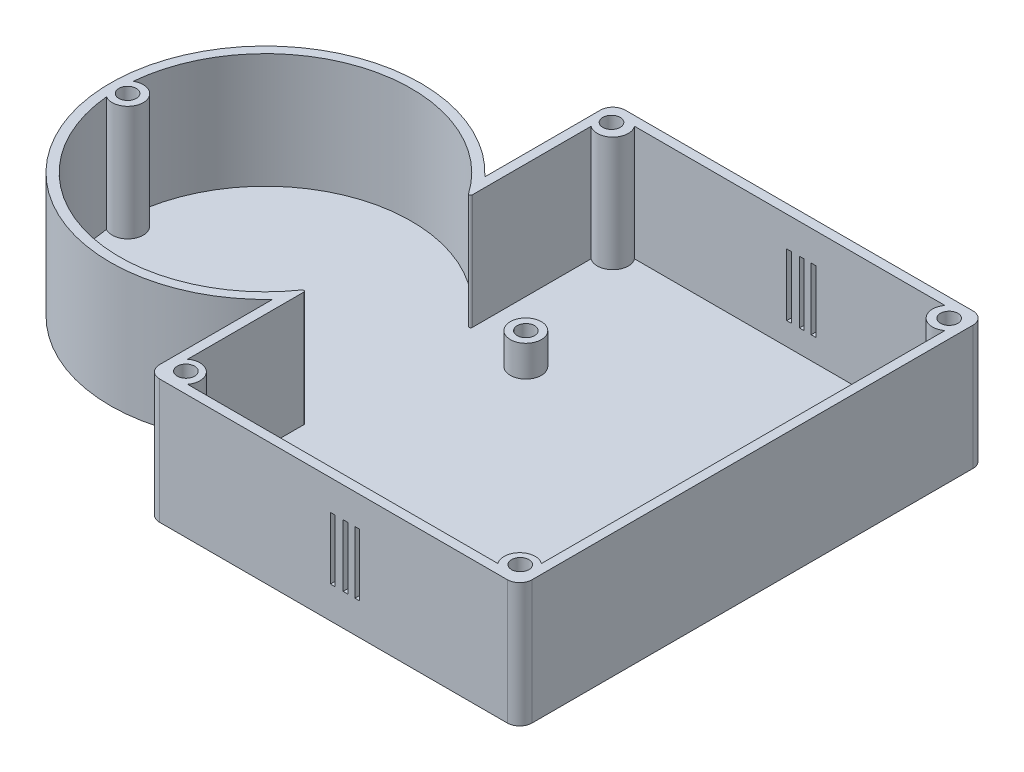
SolidWorks part; units mm, degrees
ref_plane "Front Plane" through (0, 0, 0) normal (0, 0, 1) x (1, 0, 0)
ref_plane "Top Plane" through (0, 0, 0) normal (0, 1, 0) x (1, 0, 0)
ref_plane "Right Plane" through (0, 0, 0) normal (1, 0, 0) x (0, 0, -1)
sketch "Sketch1" plane through (0, 0, 0) normal (0, 1, 0) x (1, 0, 0)
  line L0 (240.8148, 785.6528) -> (1635.5674, 785.6528) construction
sketch "Sketch8" plane through (0, 0, 0) normal (0, 1, 0) x (1, 0, 0)
  line L1 (13.7089, 147.1642) -> (133.7089, 147.1642)
  line L2 (13.7089, 147.1642) -> (13.7089, -2.8358)
  line L3 (13.7089, -2.8358) -> (133.7089, -2.8358)
  line L4 (133.7089, 147.1642) -> (133.7089, -2.8358)
  line L5 (13.7089, 147.1642) -> (133.7089, -2.8358) construction
  line L6 (13.7089, -2.8358) -> (133.7089, 147.1642) construction
  arc A0 (13.7103, 107.7112) -> (14.0464, 36.6131) centre (-21.2814, 71.9959) ccw
  point P0 (73.7089, 72.1642)
  point P5 (73.6501, 72.2835)
  point P6 (-21.2911, 72.0742)
  dimension "D1" = 120
  dimension "D2" = 150
  dimension "D3" = 95
extrude "Boss-Extrude3" add sketch "Sketch8" along normal blind 40 contours L1 L4 L3 L2
sketch "Sketch9" plane through (0, 0, 0) normal (0, 1, 0) x (1, 0, 0)
  circle A0 centre (-22.779, 71.7485) radius 50
extrude "Boss-Extrude4" add sketch "Sketch9" along normal blind 40
shell "Shell1" thickness 3 removed face at (39.2942, 40, -72.0256)
sketch "Sketch11" plane through (0, 0, 0) normal (0, 0, 1) x (1, 0, 0)
  line L5 (72.7415, 30.2907) -> (74.2415, 30.2907)
  line L6 (72.7415, 30.2907) -> (72.7415, 10.2907)
  line L7 (72.7415, 10.2907) -> (74.2415, 10.2907)
  line L8 (74.2415, 30.2907) -> (74.2415, 10.2907)
  line L9 (72.7415, 30.2907) -> (74.2415, 10.2907) construction
  line L10 (72.7415, 10.2907) -> (74.2415, 30.2907) construction
  point P0 (73.4915, 20.2907)
  dimension "D1" = 20
  dimension "D2" = 1.5
sketch "Sketch12" plane through (0, 0, 2.8358) normal (0, 0, 1) x (1, 0, 0)
  line L1 (76.8389, 30.2907) -> (78.3389, 30.2907)
  line L2 (76.8389, 30.2907) -> (76.8389, 10.2907)
  line L3 (76.8389, 10.2907) -> (78.3389, 10.2907)
  line L4 (78.3389, 30.2907) -> (78.3389, 10.2907)
  line L5 (76.8389, 30.2907) -> (78.3389, 10.2907) construction
  line L6 (76.8389, 10.2907) -> (78.3389, 30.2907) construction
  point P0 (77.5889, 20.2907)
  dimension "D1" = 20
  dimension "D2" = 1.5
sketch "Sketch15" plane through (0, 0, 0) normal (0, 0, 1) x (1, 0, 0)
  line L1 (80.6291, 30.2907) -> (82.1291, 30.2907)
  line L2 (80.6291, 30.2907) -> (80.6291, 10.2907)
  line L3 (80.6291, 10.2907) -> (82.1291, 10.2907)
  line L4 (82.1291, 30.2907) -> (82.1291, 10.2907)
  line L5 (80.6291, 30.2907) -> (82.1291, 10.2907) construction
  line L6 (80.6291, 10.2907) -> (82.1291, 30.2907) construction
  point P0 (81.3791, 20.2907)
  dimension "D1" = 1.5
  dimension "D2" = 20
sketch "Sketch17" plane through (1.8488, 3, -2.465) normal (0, 1, 0) x (1, 0, 0)
  circle A0 centre (111.867, 11.1753) radius 5
  circle A5 centre (34.367, 11.1753) radius 5
  circle A6 centre (111.867, 94.1753) radius 5
  circle A7 centre (34.367, 94.1753) radius 5
  dimension "D7" = 83
  dimension "D4" = 77.5
  dimension "D6" = 83
  dimension "D8" = 77.5
extrude "Boss-Extrude6" add sketch "Sketch17" along normal blind 10
sketch "Sketch23" plane through (0, 0, 0) normal (0, 0, 1) x (1, 0, 0)
extrude "Cut-Extrude9" cut sketch "Sketch11" against normal through all both and the other way through all contours L8 L7 L6 L5
extrude "Cut-Extrude10" cut sketch "Sketch12" against normal through all both and the other way through all contours L4 L3 L2 L1
extrude "Cut-Extrude11" cut sketch "Sketch15" against normal through all both and the other way through all contours L4 L3 L2 L1
sketch "Sketch21" plane through (0, 0, 0) normal (0, 0, 1) x (1, 0, 0)
sketch "Sketch27" plane through (0, 0, 0) normal (0, 1, 0) x (1, 0, 0)
sketch "Sketch28" plane through (0, 3, 0) normal (0, 1, 0) x (1, 0, 0)
  line L0 (13.7089, 147.1642) -> (13.7089, 105.9338) construction
  line L1 (13.7089, 147.1642) -> (133.7089, 147.1642) construction
  circle A0 centre (19.7089, 141.1642) radius 5
  dimension "D1" = 6
  dimension "D2" = 6
extrude "Boss-Extrude7" add sketch "Sketch28" along normal blind 37
sketch "Sketch29" plane through (0, 0, 0) normal (0, 1, 0) x (1, 0, 0)
  line L0 (13.7089, 37.5631) -> (13.7089, -2.8358) construction
  line L1 (13.7089, -2.8358) -> (133.7089, -2.8358) construction
  circle A0 centre (19.7089, 3.1642) radius 5
  dimension "D1" = 6
  dimension "D2" = 6
extrude "Boss-Extrude8" add sketch "Sketch29" along normal blind 40
sketch "Sketch30" plane through (0, 0, 0) normal (0, 1, 0) x (1, 0, 0)
  line L0 (133.7089, 147.1642) -> (133.7089, -2.8358) construction
  line L1 (13.7089, 147.1642) -> (133.7089, 147.1642) construction
  circle A0 centre (127.7089, 141.1642) radius 5
  dimension "D1" = 6
  dimension "D2" = 6
extrude "Boss-Extrude9" add sketch "Sketch30" along normal blind 40
sketch "Sketch31" plane through (0, 3, 0) normal (0, 1, 0) x (1, 0, 0)
  line L0 (133.7089, 147.1642) -> (133.7089, -2.8358) construction
  line L1 (13.7089, -2.8358) -> (133.7089, -2.8358) construction
  circle A0 centre (127.7089, 3.1642) radius 5
  dimension "D1" = 6
  dimension "D2" = 6
extrude "Boss-Extrude10" add sketch "Sketch31" along normal blind 37
sketch "Sketch32" plane through (0, 3, 0) normal (0, 1, 0) x (1, 0, 0)
  circle A0 centre (-67.0185, 71.629) radius 5
extrude "Boss-Extrude11" add sketch "Sketch32" along normal blind 37
hole_wizard "#2 (0.221) Diameter Hole1" positions "Sketch34" profile "Sketch35" hole size "#2" standard "ANSI Inch"
sketch "Sketch34" plane through (0, 40, 0) normal (0, 1, 0) x (1, 0, 0)
  point P0 (18.9171, 141.5314)
  point P2 (127.97, 141.2692)
  point P4 (127.6025, 3.4533)
  point P6 (19.7741, 3.5706)
  point P8 (-67.1156, 71.6687)
sketch "Sketch35" plane through (18.9171, 40, -141.5314) normal (1, 0, 0) x (0, 0, 1)
  line L0 (0, 0) -> (0, 9.6864)
  line L1 (0, 9.6864) -> (2.8067, 8)
  line L2 (2.8067, 8) -> (2.8067, 0)
  line L5 (2.8067, 0) -> (0, 0)
  line L10 (0, 9.6864) -> (-2.8067, 8) construction
  line L11 (0, -6.35) -> (0, 107.95) construction
  dimension "Hole Dia." = 5.6134
  dimension "Hole Depth" = 8
  dimension "Drill Angle" = 118
hole_wizard "#2 (0.221) Diameter Hole2" positions "Sketch36" profile "Sketch37" hole size "#2" standard "ANSI Inch"
sketch "Sketch36" plane through (0, 13, 0) normal (0, 1, 0) x (1, 0, 0)
  point P2 (113.8666, 96.6657)
  point P4 (36.2691, 13.6724)
  point P6 (113.8666, 13.4154)
  point P14 (36.2247, 96.6373)
sketch "Sketch37" plane through (113.8666, 13, -96.6657) normal (1, 0, 0) x (0, 0, 1)
  line L0 (0, 0) -> (0, 9.6864)
  line L1 (0, 9.6864) -> (2.8067, 8)
  line L2 (2.8067, 8) -> (2.8067, 0)
  line L5 (2.8067, 0) -> (0, 0)
  line L10 (0, 9.6864) -> (-2.8067, 8) construction
  line L11 (0, -6.35) -> (0, 107.95) construction
  dimension "Hole Dia." = 5.6134
  dimension "Hole Depth" = 8
  dimension "Drill Angle" = 118
fillet "Fillet3" radius 4 4 edges at (133.7089, 20, 2.8358) (133.7089, 20, -147.1642) (13.7089, 20, 2.8358) (13.7089, 20, -147.1642)
fillet "Fillet2" radius 0.5 2 edges at (16.7089, 21.5, -46.2591) (16.7089, 21.5, -97.2378)
